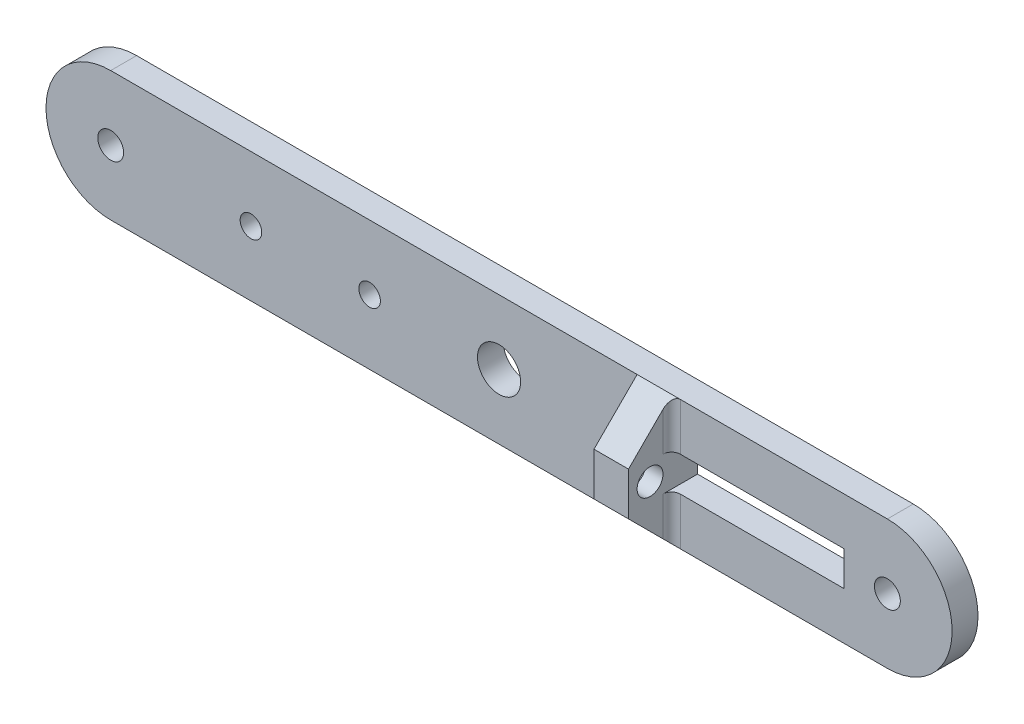
SolidWorks part; units mm, degrees
ref_plane "Plan de face" through (0, 0, 0) normal (0, 0, 1) x (1, 0, 0)
ref_plane "Plan de dessus" through (0, 0, 0) normal (0, 1, 0) x (1, 0, 0)
ref_plane "Plan de droite" through (0, 0, 0) normal (1, 0, 0) x (0, 0, -1)
sketch "Esquisse1" plane through (0, 0, 0) normal (0, 0, 1) x (1, 0, 0)
  line L0 (-74.3787, 0) -> (69.7437, 0) construction
  line L1 (0, 0) -> (0, 19.0596) construction
  line L2 (90, -15) -> (-90, -15)
  line L3 (90, 15) -> (-90, 15)
  line L5 (40, -4) -> (80, -4)
  line L6 (40, -4) -> (40, 4)
  line L7 (40, 4) -> (80, 4)
  line L8 (80, -4) -> (80, 4)
  line L9 (40, -4) -> (80, 4) construction
  line L10 (40, 4) -> (80, -4) construction
  arc A0 (90, -15) -> (90, 15) centre (90, 0) ccw
  circle A1 centre (90, 0) radius 3
  circle A2 centre (-90, 0) radius 3
  arc A3 (-90, -15) -> (-90, 15) centre (-90, 0) cw
  circle A4 centre (0, 0) radius 5
  circle A5 centre (-57.5, 0) radius 2.5
  circle A6 centre (-30, 0) radius 2.5
  point P4 (60, 0)
  point P17 (0, -15)
  point P20 (0, 15)
  dimension "D1" = 30
  dimension "D3" = 6
  dimension "D7" = 10
  dimension "D8" = 5
  dimension "D9" = 5
  dimension "D2" = 90
  dimension "D4" = 8
  dimension "D5" = 40
  dimension "D6" = 60
  dimension "D10" = 30
  dimension "D11" = 30
extrude "Boss.-Extru.1" add sketch "Esquisse1" along normal blind 6
sketch "Esquisse2" plane through (40, 0, 0) normal (1, 0, 0) x (0, 0, -1)
  line L0 (0, -4) -> (-6, 4) construction
  line L1 (-6, 4) -> (-6, 0) construction
  line L2 (-6, 4) -> (-6, -4) construction
  line L3 (-6, 0) -> (-15.5036, 0) construction
  line L4 (-6, 15) -> (-6, -15) construction
  line L6 (-16, 5) -> (-16, -5)
  line L8 (-6, 5) -> (-6, -5)
  line L9 (-16, 5) -> (-6, -5) construction
  line L10 (-16, -5) -> (-6, 5) construction
  line L11 (-6, -15) -> (-16, -5)
  line L12 (-6, -15) -> (-6, -5)
  line L13 (-6, 5) -> (-6, 15)
  line L14 (-6, 15) -> (-16, 5)
  circle A0 centre (-11, 0) radius 3
  point P7 (-11, 0)
  dimension "D3" = 6
  dimension "D1" = 10
  dimension "D2" = 10
extrude "Boss.-Extru.2" add sketch "Esquisse2" against normal blind 8
fillet "Congé2" radius 2 2 edges
sketch "Esquisse3" plane through (32, 0, 0) normal (-1, 0, 0) x (0, 0, 1)
  line L0 (11, 0) -> (11, 4) construction
  line L1 (11, 0) -> (14.4641, 2) construction
  line L2 (11, 0) -> (14.4641, -2) construction
  line L3 (11, 4) -> (14.4641, 2)
  line L4 (14.4641, 2) -> (14.4641, -2)
  line L5 (14.4641, -2) -> (11, -4)
  line L6 (7.5359, 2) -> (7.5359, -2)
  line L7 (11, 4) -> (7.5359, 2)
  line L8 (7.5359, -2) -> (11, -4)
  dimension "D2" = 60
  dimension "D3" = 60
extrude "Enlèv. mat.-Extru.1" cut sketch "Esquisse3" against normal blind 4
